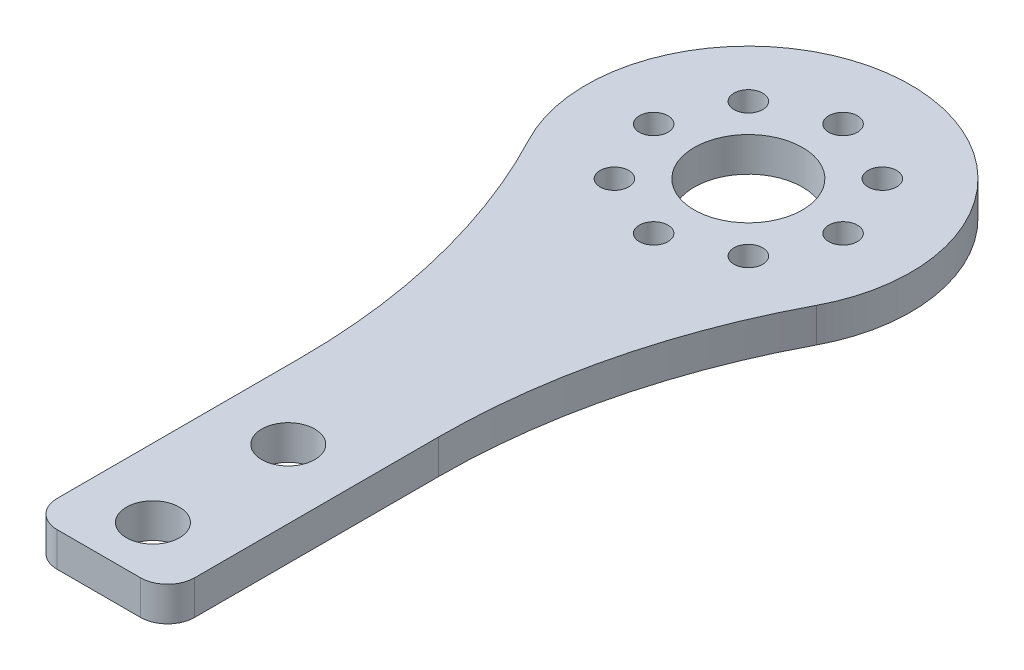
SolidWorks part; units mm, degrees
material "1060 Alloy"
ref_plane "Front Plane" through (0, 0, 0) normal (0, 0, 1) x (1, 0, 0)
ref_plane "Top Plane" through (0, 0, 0) normal (0, 1, 0) x (1, 0, 0)
ref_plane "Right Plane" through (0, 0, 0) normal (1, 0, 0) x (0, 0, -1)
sketch "Sketch1" plane through (0, 0, 0) normal (0, 1, 0) x (1, 0, 0)
  line L0 (-12.7, -120) -> (12.7, -120)
  line L1 (12.7, -120) -> (12.7, -27.1792)
  line L2 (-12.7, -120) -> (-12.7, -27.1792)
  line L3 (0, -120) -> (0, -85) construction
  arc A0 (12.7, -27.1792) -> (-12.7, -27.1792) centre (0, 0) ccw
  point P1 (0, -85)
  point P5 (0, -120)
  point P7 (0, -110)
  dimension "D2" = 60
  dimension "D1" = 25.4
  dimension "D3" = 85
  dimension "D4" = 25
  dimension "D5" = 10
extrude "Boss-Extrude1" add sketch "Sketch1" along normal blind 6.35 contours A0 L2 L0 L1
sketch "Sketch2" plane through (0, 0, 0) normal (0, -1, 0) x (1, 0, 0)
  circle A0 centre (0, 0) radius 17.5 construction
  point P3 (17.5, 0)
  point P6 (12.3744, -12.3744)
  point P7 (0, -17.5)
  point P8 (-12.3744, -12.3744)
  point P9 (-17.5, 0)
  point P10 (-12.3744, 12.3744)
  point P11 (0, 17.5)
  point P12 (12.3744, 12.3744)
  point P13 (0, 0)
  dimension "D2" = 35
  dimension "D1" = 8
hole_wizard "M5 Clearance Hole1" positions "Sketch3" profile "Sketch4" hole size "M5" standard "ANSI Metric" end condition through all
sketch "Sketch3" plane through (0, 0, 0) normal (0, -1, 0) x (-1, 0, 0)
  point P0 (0, 17.5)
  point P3 (12.3744, 12.3744)
  point P6 (17.5, 0)
  point P9 (12.3744, -12.3744)
  point P12 (0, -17.5)
  point P15 (-12.3744, -12.3744)
  point P18 (-17.5, 0)
  point P21 (-12.3744, 12.3744)
sketch "Sketch4" plane through (0, 0, -17.5) normal (1, 0, 0) x (0, 0, -1)
  line L0 (0, 0) -> (0, 6.35)
  line L1 (0, 6.35) -> (2.65, 6.35)
  line L2 (2.65, 6.35) -> (2.65, 0)
  line L5 (2.65, 0) -> (0, 0)
  line L11 (0, -6.35) -> (0, 107.95) construction
  dimension "Thru Hole Dia." = 5.3
  dimension "Thru Hole Depth" = 6.35
sketch "Sketch5" plane through (0, 0, 0) normal (0, -1, 0) x (1, 0, 0)
  circle A0 centre (0, 0) radius 10
  dimension "D1" = 20
extrude "Cut-Extrude1" cut sketch "Sketch5" against normal through all
hole_wizard "3/8 Clearance Hole1" positions "Sketch9" profile "Sketch11" hole size "3/8" standard "ANSI Inch" end condition through all
sketch "Sketch9" plane through (0, 0, 0) normal (0, -1, 0) x (-1, 0, 0)
  point P0 (0, -85)
  point P3 (0, -110)
sketch "Sketch11" plane through (0, 0, 85) normal (1, 0, 0) x (0, 0, -1)
  line L0 (0, 0) -> (0, 6.35)
  line L1 (0, 6.35) -> (4.9022, 6.35)
  line L2 (4.9022, 6.35) -> (4.9022, 0)
  line L5 (4.9022, 0) -> (0, 0)
  line L11 (0, -6.35) -> (0, 107.95) construction
  dimension "Thru Hole Dia." = 9.8044
  dimension "Thru Hole Depth" = 6.35
fillet "Fillet1" radius 120 2 edges at (-12.7, 3.175, 27.1792) (12.7, 3.175, 27.1792)
fillet "Fillet2" radius 5 2 edges at (12.7, 3.175, 120) (-12.7, 3.175, 120)
